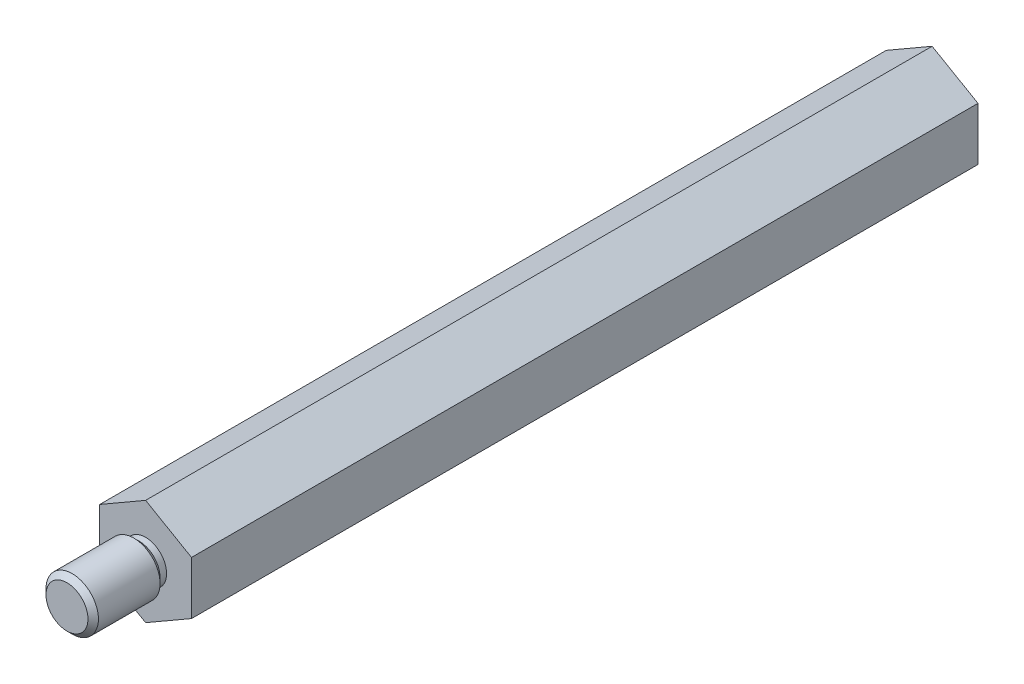
SolidWorks part; units mm, degrees
ref_plane "Спереди" through (0, 0, 0) normal (0, 0, 1) x (1, 0, 0)
ref_plane "Сверху" through (0, 0, 0) normal (0, 1, 0) x (1, 0, 0)
ref_plane "Справа" through (0, 0, 0) normal (1, 0, 0) x (0, 0, -1)
sketch "Эскиз1" plane through (0, 0, 0) normal (0, 0, 1) x (1, 0, 0)
  line L1 (0, 4.0415) -> (-3.5, 2.0207)
  line L2 (-3.5, 2.0207) -> (-3.5, -2.0207)
  line L3 (-3.5, -2.0207) -> (0, -4.0415)
  line L4 (0, -4.0415) -> (3.5, -2.0207)
  line L5 (3.5, -2.0207) -> (3.5, 2.0207)
  line L6 (3.5, 2.0207) -> (0, 4.0415)
  circle A0 centre (0, 0) radius 3.5 construction
  dimension "D1" = 7
extrude "Вытянуть1" add sketch "Эскиз1" along normal blind 60
sketch "Эскиз2" plane through (0, 0, 60) normal (0, 0, 1) x (1, 0, 0)
  circle A0 centre (0, 0) radius 2
  dimension "D1" = 4
extrude "Вытянуть2" add sketch "Эскиз2" along normal blind 6
sketch "Эскиз3" plane through (0, 0, 60) normal (0, 0, 1) x (1, 0, 0)
  circle A0 centre (0, 0) radius 1.6
  circle A1 centre (0, 0) radius 2 construction
  circle A2 centre (0, 0) radius 2
  dimension "D1" = 3.2
extrude "Вырез-Вытянуть3" cut sketch "Эскиз3" along normal blind 0.5
chamfer "Фаска1" distance 0.4 angle 45 2 edges at (2, 0, 60.5) (2, 0, 66)
hole_wizard "Отверстие с зазором M31" positions "Трехмерный эскиз2" profile "Эскиз5" hole size "M3" standard "Ansi Метрический"
sketch3d "Трехмерный эскиз2"
  point P0 (0, 0, 0)
  point P2 (0, 0, 0)
  point P3 (0, 0, 0)
sketch "Эскиз5" plane through (0, 0, 0) normal (1, 0, 0) x (0, 1, 0)
  line L0 (0, 0) -> (0, 10.9614)
  line L1 (0, 10.9614) -> (1.6, 10)
  line L2 (1.6, 10) -> (1.6, 0.4)
  line L3 (1.6, 0.4) -> (2, 0)
  line L5 (2, 0) -> (0, 0)
  line L6 (-1.6, 0.4) -> (-2, 0) construction
  line L10 (0, 10.9614) -> (-1.6, 10) construction
  line L11 (0, -6.35) -> (0, 107.95) construction
  dimension "Диаметр отверстия" = 3.2
  dimension "Глубина отверстия" = 10
  dimension "Диаметр передней зенковки" = 4
  dimension "Угол передней зенковки" = 90
  dimension "Угол заточки сверла" = 118
cosmetic thread "Условное изображение резьбы1" parameters "D1"=8, "D2"=4
